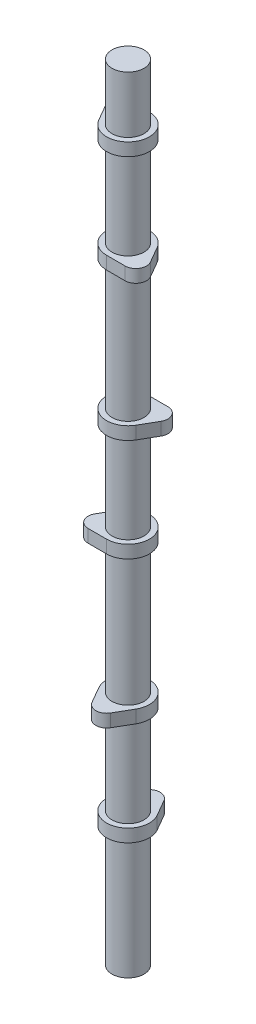
SolidWorks part; units mm, degrees
ref_plane "Front Plane" through (0, 0, 0) normal (0, 0, 1) x (1, 0, 0)
ref_plane "Top Plane" through (0, 0, 0) normal (0, 1, 0) x (1, 0, 0)
ref_plane "Right Plane" through (0, 0, 0) normal (1, 0, 0) x (0, 0, -1)
sketch "Sketch1" plane through (0, 0, 0) normal (0, 1, 0) x (1, 0, 0)
  line L0 (-5.4993, 15.875) -> (-10.9985, 6.35)
  line L1 (5.4993, 15.875) -> (10.9985, 6.35)
  arc A0 (-10.9985, 6.35) -> (10.9985, 6.35) centre (0, 0) ccw
  arc A1 (5.4993, 15.875) -> (-5.4993, 15.875) centre (0, 12.7) ccw
  dimension "D1" = 25.4
  dimension "D2" = 12.7
  dimension "D3" = 12.7
extrude "Boss-Extrude1" add sketch "Sketch1" along normal mid plane 7.62
ref_axis "Axis1" through (0, 176.0944, 0) along (0, -1, 0)
move or copy body "Body-Move/Copy1" bodies to move or copy 101 copy yes number of copies 1 translate (0, 60.96, 0)
move or copy body "Body-Move/Copy2" bodies to move or copy 102 copy no rotation origin (0, 0, 0) rotation axis (0, 1, 0) rotation angle 180
sketch "Sketch2" plane through (0, 0, 0) normal (0, 1, 0) x (1, 0, 0)
  circle A0 centre (0, 0) radius 9.5
  dimension "D1" = 19
extrude "Boss-Extrude2" add sketch "Sketch2" along normal mid plane 146.05 from offset 25.4
pattern_linear "LPattern1" count 3 spacing 146.05 along (0, 1, 0) of bodies 104
move or copy body "Body-Move/Copy3" bodies to move or copy 105 copy no rotation origin (0, 0, 0) rotation axis (0, 1, 0) rotation angle 120
move or copy body "Body-Move/Copy4" bodies to move or copy 106 copy no rotation origin (0, 0, 0) rotation axis (0, -1, 0) rotation angle 120
sketch "Sketch3" plane through (0, -47.625, 0) normal (0, -1, 0) x (1, 0, 0)
  circle A1 centre (0, 0) radius 9.5
  circle A2 centre (0, 0) radius 9.5
  dimension "D1" = 0
extrude "Boss-Extrude3" add sketch "Sketch3" along normal blind 27.94
combine bodies "Combine1" operation type add bodies to combine 109 107 108
scale "Scale1" scale about centroid uniform scaling yes scale factor 0.51948
